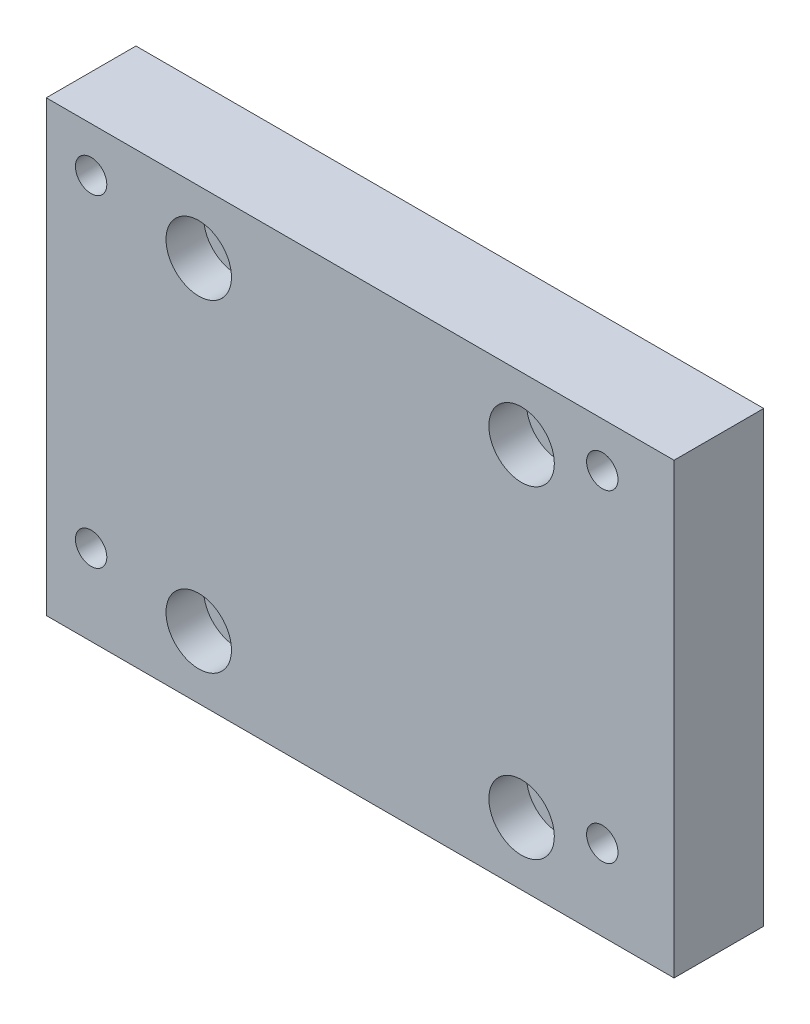
SolidWorks part; units mm, degrees
ref_plane "前基準面" through (0, 0, 0) normal (0, 0, 1) x (1, 0, 0)
ref_plane "上基準面" through (0, 0, 0) normal (0, 1, 0) x (1, 0, 0)
ref_plane "右基準面" through (0, 0, 0) normal (1, 0, 0) x (0, 0, -1)
sketch "草圖2" plane through (0, 0, 0) normal (0, 0, 1) x (1, 0, 0)
  line L0 (0, 0) -> (0, 30.0174) construction
  line L1 (-35, 25) -> (35, 25)
  line L2 (-35, 25) -> (-35, -25)
  line L3 (-35, -25) -> (35, -25)
  line L4 (35, 25) -> (35, -25)
  line L5 (-35, 25) -> (35, -25) construction
  line L6 (-35, -25) -> (35, 25) construction
  line L7 (0, -55) -> (0, 55) construction
  line L8 (0, 0) -> (-44.8344, 0) construction
  line L9 (55, 0) -> (-55, 0) construction
  line L10 (57, 0) -> (12.1656, 0) construction
  line L11 (57, -36) -> (12.1656, -36) construction
  line L12 (0, -36) -> (-44.8344, -36) construction
  circle A0 centre (-18, 18) radius 2.25
  circle A1 centre (-30, 20) radius 1.75
  circle A2 centre (18, 18) radius 2.25
  circle A3 centre (18, -18) radius 2.25
  circle A4 centre (-18, -18) radius 2.25
  circle A5 centre (27, 20) radius 1.75
  circle A6 centre (27, -16) radius 1.75
  circle A7 centre (-30, -16) radius 1.75
  point P0 (0, 0)
  dimension "D3" = 4.5
  dimension "D6" = 3.5
  dimension "D9" = 30
  dimension "D10" = 20
  dimension "D1" = 70
  dimension "D2" = 50
  dimension "D4" = 36
  dimension "D5" = 36
  dimension "D7" = 2
  dimension "D8" = 2
extrude "填料-伸長1" add sketch "草圖2" along normal blind 10
hole_wizard "鑽孔1" positions "3D草圖1" profile "草圖3" legacy end condition through all
sketch3d "3D草圖1"
  line L0 (-18, 18, 10) -> (-18, 18, 0) construction
  line L1 (18, 18, 10) -> (18, 18, 0) construction
  line L2 (18, -18, 10) -> (18, -18, 0) construction
  line L3 (-18, -18, 10) -> (-18, -18, 0) construction
  point P0 (-18, 18, 10)
  point P4 (18, 18, 10)
  point P8 (18, -18, 10)
  point P12 (-18, -18, 10)
sketch "草圖3" plane through (-18, 18, 10) normal (1, 0, 0) x (0, -1, 0)
  line L0 (0, 0) -> (0, 10)
  line L1 (0, 10) -> (2.25, 10)
  line L2 (2.25, 10) -> (2.25, 4.2)
  line L3 (2.25, 4.2) -> (3.65, 4.2)
  line L4 (3.65, 4.2) -> (3.65, 0)
  line L5 (3.65, 0) -> (0, 0)
  line L6 (0, 110) -> (0, -10) construction
  dimension "直徑" = 4.5
  dimension "深度" = 10
  dimension "柱孔直徑1" = 7.3
  dimension "柱孔深度1" = 4.2
sketch "草圖4" plane through (0, 0, 0) normal (0, 0, -1) x (-1, 0, 0)
  line L1 (-23.7091, 20) -> (-25.3546, 22.85)
  line L2 (-25.3546, 22.85) -> (-28.6454, 22.85)
  line L3 (-28.6454, 22.85) -> (-30.2909, 20)
  line L4 (-30.2909, 20) -> (-28.6454, 17.15)
  line L5 (-28.6454, 17.15) -> (-25.3546, 17.15)
  line L6 (-25.3546, 17.15) -> (-23.7091, 20)
  line L7 (26.7091, 20) -> (28.3546, 17.15)
  line L8 (28.3546, 17.15) -> (31.6454, 17.15)
  line L9 (31.6454, 17.15) -> (33.2909, 20)
  line L10 (33.2909, 20) -> (31.6454, 22.85)
  line L11 (31.6454, 22.85) -> (28.3546, 22.85)
  line L12 (28.3546, 22.85) -> (26.7091, 20)
  line L13 (26.7091, -16) -> (28.3546, -18.85)
  line L14 (28.3546, -18.85) -> (31.6454, -18.85)
  line L15 (31.6454, -18.85) -> (33.2909, -16)
  line L16 (33.2909, -16) -> (31.6454, -13.15)
  line L17 (31.6454, -13.15) -> (28.3546, -13.15)
  line L18 (28.3546, -13.15) -> (26.7091, -16)
  line L19 (-23.7091, -16) -> (-25.3546, -13.15)
  line L20 (-25.3546, -13.15) -> (-28.6454, -13.15)
  line L21 (-28.6454, -13.15) -> (-30.2909, -16)
  line L22 (-30.2909, -16) -> (-28.6454, -18.85)
  line L23 (-28.6454, -18.85) -> (-25.3546, -18.85)
  line L24 (-25.3546, -18.85) -> (-23.7091, -16)
  circle A0 centre (-27, 20) radius 2.85 construction
  circle A1 centre (30, 20) radius 2.85 construction
  circle A2 centre (30, -16) radius 2.85 construction
  circle A3 centre (-27, -16) radius 2.85 construction
  point P28 (0, 0)
  point P37 (0, 0)
  point P38 (0, 0)
  point P39 (0, 0)
  dimension "D1" = 5.7
extrude "除料-伸長1" cut sketch "草圖4" against normal blind 2.5
